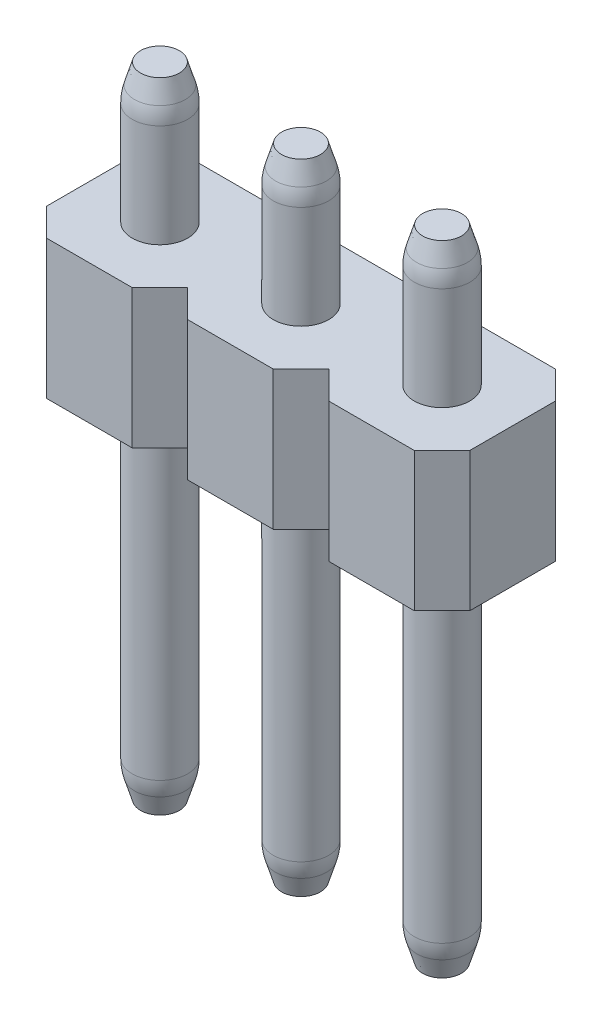
SolidWorks part; units mm, degrees
material "Brass"
ref_plane "Front Plane" through (0, 0, 0) normal (0, 0, 1) x (1, 0, 0)
ref_plane "Top Plane" through (0, 0, 0) normal (0, 1, 0) x (1, 0, 0)
ref_plane "Right Plane" through (0, 0, 0) normal (1, 0, 0) x (0, 0, -1)
sketch "Sketch1" plane through (0, 0, 0) normal (0, 1, 0) x (1, 0, 0)
  line L0 (0, 0) -> (2.54, 0) construction
  circle A0 centre (0, 0) radius 0.5
  circle A1 centre (2.54, 0) radius 0.5
  circle A2 centre (5.08, 0) radius 0.5
  circle A3 centre (7.62, 0) radius 0.5
  circle A4 centre (10.16, 0) radius 0.5
  circle A5 centre (12.7, 0) radius 0.5
  circle A6 centre (15.24, 0) radius 0.5
  circle A7 centre (17.78, 0) radius 0.5
  circle A8 centre (20.32, 0) radius 0.5
  circle A9 centre (22.86, 0) radius 0.5
  circle A10 centre (25.4, 0) radius 0.5
  circle A11 centre (27.94, 0) radius 0.5
  circle A12 centre (30.48, 0) radius 0.5
  circle A13 centre (33.02, 0) radius 0.5
  circle A14 centre (35.56, 0) radius 0.5
  circle A15 centre (38.1, 0) radius 0.5
  dimension "D1" = 1
  dimension "D3" = 2.54
  dimension "D2" = 16
extrude "Boss-Extrude1" add sketch "Sketch1" along normal blind 11.5
ref_plane "Plane1" through (0, 6.5, 0) normal (0, 1, 0) x (1, 0, 0)
sketch "Sketch2" plane through (0, 6.5, 0) normal (0, 1, 0) x (1, 0, 0)
  line L0 (-1.27, 0.77) -> (-0.77, 1.27)
  line L1 (-0.77, -1.27) -> (0.77, -1.27)
  line L2 (-1.27, -0.77) -> (-1.27, 0.77)
  line L3 (-0.77, 1.27) -> (0.77, 1.27)
  line L5 (-1.27, -1.27) -> (1.27, 1.27) construction
  line L6 (-1.27, 1.27) -> (1.27, -1.27) construction
  line L7 (0.77, 1.27) -> (1.27, 0.77)
  line L8 (0.77, -1.27) -> (1.27, -0.77)
  line L9 (-1.27, -0.77) -> (-0.77, -1.27)
  line L10 (1.27, 0.77) -> (1.77, 1.27)
  line L11 (1.77, 1.27) -> (3.31, 1.27)
  line L12 (3.31, 1.27) -> (3.81, 0.77)
  line L14 (3.31, -1.27) -> (3.81, -0.77)
  line L15 (1.77, -1.27) -> (3.31, -1.27)
  line L16 (1.27, -0.77) -> (1.77, -1.27)
  line L17 (3.81, 0.77) -> (4.31, 1.27)
  line L18 (4.31, 1.27) -> (5.85, 1.27)
  line L19 (5.85, 1.27) -> (6.35, 0.77)
  line L20 (6.35, -0.77) -> (6.35, 0.77) construction
  line L21 (5.85, -1.27) -> (6.35, -0.77)
  line L22 (4.31, -1.27) -> (5.85, -1.27)
  line L23 (3.81, -0.77) -> (4.31, -1.27)
  line L24 (6.35, 0.77) -> (6.85, 1.27)
  line L25 (6.85, 1.27) -> (8.39, 1.27)
  line L26 (8.39, 1.27) -> (8.89, 0.77)
  line L27 (8.89, -0.77) -> (8.89, 0.77) construction
  line L28 (8.39, -1.27) -> (8.89, -0.77)
  line L29 (6.85, -1.27) -> (8.39, -1.27)
  line L30 (6.35, -0.77) -> (6.85, -1.27)
  line L31 (8.89, 0.77) -> (9.39, 1.27)
  line L32 (9.39, 1.27) -> (10.93, 1.27)
  line L33 (10.93, 1.27) -> (11.43, 0.77)
  line L34 (11.43, -0.77) -> (11.43, 0.77) construction
  line L35 (10.93, -1.27) -> (11.43, -0.77)
  line L36 (9.39, -1.27) -> (10.93, -1.27)
  line L37 (8.89, -0.77) -> (9.39, -1.27)
  line L38 (11.43, 0.77) -> (11.93, 1.27)
  line L39 (11.93, 1.27) -> (13.47, 1.27)
  line L40 (13.47, 1.27) -> (13.97, 0.77)
  line L41 (13.97, -0.77) -> (13.97, 0.77) construction
  line L42 (13.47, -1.27) -> (13.97, -0.77)
  line L43 (11.93, -1.27) -> (13.47, -1.27)
  line L44 (11.43, -0.77) -> (11.93, -1.27)
  line L45 (13.97, 0.77) -> (14.47, 1.27)
  line L46 (14.47, 1.27) -> (16.01, 1.27)
  line L47 (16.01, 1.27) -> (16.51, 0.77)
  line L48 (16.51, -0.77) -> (16.51, 0.77) construction
  line L49 (16.01, -1.27) -> (16.51, -0.77)
  line L50 (14.47, -1.27) -> (16.01, -1.27)
  line L51 (13.97, -0.77) -> (14.47, -1.27)
  line L52 (16.51, 0.77) -> (17.01, 1.27)
  line L53 (17.01, 1.27) -> (18.55, 1.27)
  line L54 (18.55, 1.27) -> (19.05, 0.77)
  line L55 (19.05, -0.77) -> (19.05, 0.77) construction
  line L56 (18.55, -1.27) -> (19.05, -0.77)
  line L57 (17.01, -1.27) -> (18.55, -1.27)
  line L58 (16.51, -0.77) -> (17.01, -1.27)
  line L59 (19.05, 0.77) -> (19.55, 1.27)
  line L60 (19.55, 1.27) -> (21.09, 1.27)
  line L61 (21.09, 1.27) -> (21.59, 0.77)
  line L62 (21.59, -0.77) -> (21.59, 0.77) construction
  line L63 (21.09, -1.27) -> (21.59, -0.77)
  line L64 (19.55, -1.27) -> (21.09, -1.27)
  line L65 (19.05, -0.77) -> (19.55, -1.27)
  line L66 (21.59, 0.77) -> (22.09, 1.27)
  line L67 (22.09, 1.27) -> (23.63, 1.27)
  line L68 (23.63, 1.27) -> (24.13, 0.77)
  line L69 (24.13, -0.77) -> (24.13, 0.77) construction
  line L70 (23.63, -1.27) -> (24.13, -0.77)
  line L71 (22.09, -1.27) -> (23.63, -1.27)
  line L72 (21.59, -0.77) -> (22.09, -1.27)
  line L73 (24.13, 0.77) -> (24.63, 1.27)
  line L74 (24.63, 1.27) -> (26.17, 1.27)
  line L75 (26.17, 1.27) -> (26.67, 0.77)
  line L76 (26.67, -0.77) -> (26.67, 0.77) construction
  line L77 (26.17, -1.27) -> (26.67, -0.77)
  line L78 (24.63, -1.27) -> (26.17, -1.27)
  line L79 (24.13, -0.77) -> (24.63, -1.27)
  line L80 (26.67, 0.77) -> (27.17, 1.27)
  line L81 (27.17, 1.27) -> (28.71, 1.27)
  line L82 (28.71, 1.27) -> (29.21, 0.77)
  line L83 (29.21, -0.77) -> (29.21, 0.77) construction
  line L84 (28.71, -1.27) -> (29.21, -0.77)
  line L85 (27.17, -1.27) -> (28.71, -1.27)
  line L86 (26.67, -0.77) -> (27.17, -1.27)
  line L87 (29.21, 0.77) -> (29.71, 1.27)
  line L88 (29.71, 1.27) -> (31.25, 1.27)
  line L89 (31.25, 1.27) -> (31.75, 0.77)
  line L90 (31.75, -0.77) -> (31.75, 0.77) construction
  line L91 (31.25, -1.27) -> (31.75, -0.77)
  line L92 (29.71, -1.27) -> (31.25, -1.27)
  line L93 (29.21, -0.77) -> (29.71, -1.27)
  line L94 (31.75, 0.77) -> (32.25, 1.27)
  line L95 (32.25, 1.27) -> (33.79, 1.27)
  line L96 (33.79, 1.27) -> (34.29, 0.77)
  line L97 (34.29, -0.77) -> (34.29, 0.77) construction
  line L98 (33.79, -1.27) -> (34.29, -0.77)
  line L99 (32.25, -1.27) -> (33.79, -1.27)
  line L100 (31.75, -0.77) -> (32.25, -1.27)
  line L101 (34.29, 0.77) -> (34.79, 1.27)
  line L102 (34.79, 1.27) -> (36.33, 1.27)
  line L103 (36.33, 1.27) -> (36.83, 0.77)
  line L104 (36.83, -0.77) -> (36.83, 0.77) construction
  line L105 (36.33, -1.27) -> (36.83, -0.77)
  line L106 (34.79, -1.27) -> (36.33, -1.27)
  line L107 (34.29, -0.77) -> (34.79, -1.27)
  line L108 (36.83, 0.77) -> (37.33, 1.27)
  line L109 (37.33, 1.27) -> (38.87, 1.27)
  line L110 (38.87, 1.27) -> (39.37, 0.77)
  line L111 (39.37, -0.77) -> (39.37, 0.77)
  line L112 (38.87, -1.27) -> (39.37, -0.77)
  line L113 (37.33, -1.27) -> (38.87, -1.27)
  line L114 (36.83, -0.77) -> (37.33, -1.27)
  line L115 (-1.27, 0.77) -> (1.27, 0.77) construction
  point P0 (0, 0)
  dimension "D1" = 2.54
  dimension "D2" = 2.54
  dimension "D4" = 2.54
  dimension "D3" = 16
extrude "Boss-Extrude2" add sketch "Sketch2" along normal blind 2.5
chamfer "Chamfer1" distance 0.5 distance2 0.15 16 edges at (15.24, 11.5, 0.5) (12.7, 11.5, 0.5) (10.16, 11.5, 0.5) (7.62, 11.5, 0.5) (5.08, 11.5, 0.5) (2.54, 11.5, 0.5) (0, 11.5, 0.5) (38.1, 11.5, 0.5) (35.56, 11.5, 0.5) (33.02, 11.5, 0.5) (30.48, 11.5, 0.5) (27.94, 11.5, 0.5) (25.4, 11.5, 0.5) (22.86, 11.5, 0.5) (20.32, 11.5, 0.5) (17.78, 11.5, 0.5) first distance on face at (15.24, 11.5, 0.5) first distance on face at (12.7, 11.5, 0.5) first distance on face at (10.16, 11.5, 0.5) first distance on face at (7.62, 11.5, 0.5) first distance on face at (5.08, 11.5, 0.5) first distance on face at (2.54, 11.5, 0.5) first distance on face at (0, 11.5, 0.5) first distance on face at (38.1, 11.5, 0.5) first distance on face at (35.56, 11.5, 0.5) first distance on face at (33.02, 11.5, 0.5) first distance on face at (30.48, 11.5, 0.5) first distance on face at (27.94, 11.5, 0.5) first distance on face at (25.4, 11.5, 0.5) first distance on face at (22.86, 11.5, 0.5) first distance on face at (20.32, 11.5, 0.5) first distance on face at (17.78, 11.5, 0.5)
fillet "Fillet1" radius 1 16 edges at (38.1, 11, 0.5) (35.56, 11, 0.5) (33.02, 11, 0.5) (30.48, 11, 0.5) (27.94, 11, 0.5) (25.4, 11, 0.5) (22.86, 11, 0.5) (20.32, 11, 0.5) (17.78, 11, 0.5) (15.24, 11, 0.5) (12.7, 11, 0.5) (10.16, 11, 0.5) (7.62, 11, 0.5) (5.08, 11, 0.5) (2.54, 11, 0.5) (0, 11, 0.5)
chamfer "Chamfer2" distance 0.15 distance2 0.5 16 edges at (10.16, 0, 0.5) (17.78, 0, 0.5) (22.86, 0, 0.5) (27.94, 0, 0.5) (30.48, 0, 0.5) (0, 0, 0.5) (2.54, 0, 0.5) (5.08, 0, 0.5) (7.62, 0, 0.5) (12.7, 0, 0.5) (15.24, 0, 0.5) (20.32, 0, 0.5) (25.4, 0, 0.5) (33.02, 0, 0.5) (35.56, 0, 0.5) (38.1, 0, 0.5) first distance on face at (10.16, 0, 0.5) first distance on face at (17.78, 0, 0.5) first distance on face at (22.86, 0, 0.5) first distance on face at (27.94, 0, 0.5) first distance on face at (30.48, 0, 0.5) first distance on face at (0, 0, 0.5) first distance on face at (2.54, 0, 0.5) first distance on face at (5.08, 0, 0.5) first distance on face at (7.62, 0, 0.5) first distance on face at (12.7, 0, 0.5) first distance on face at (15.24, 0, 0.5) first distance on face at (20.32, 0, 0.5) first distance on face at (25.4, 0, 0.5) first distance on face at (33.02, 0, 0.5) first distance on face at (35.56, 0, 0.5) first distance on face at (38.1, 0, 0.5)
fillet "Fillet2" radius 1 16 edges at (30.48, 0.5, 0.5) (33.02, 0.5, 0.5) (35.56, 0.5, 0.5) (38.1, 0.5, 0.5) (27.94, 0.5, 0.5) (25.4, 0.5, 0.5) (22.86, 0.5, 0.5) (20.32, 0.5, 0.5) (17.78, 0.5, 0.5) (15.24, 0.5, 0.5) (12.7, 0.5, 0.5) (10.16, 0.5, 0.5) (7.62, 0.5, 0.5) (5.08, 0.5, 0.5) (2.54, 0.5, 0.5) (0, 0.5, 0.5)
sketch "Sketch3" plane through (0, 0, -1.27) normal (0, 0, -1) x (-1, 0, 0)
  line L0 (-31.75, 9) -> (-31.75, 6.5) construction
  line L1 (-31.75, 11.5) -> (-31.75, 0)
  line L2 (-24.13, 9) -> (-24.13, 6.5) construction
  line L3 (-24.13, 11.5) -> (-24.13, 0)
  line L4 (-31.75, 0) -> (-40.2825, 0)
  line L5 (-40.2825, 0) -> (-40.2825, 14.7026)
  line L6 (-40.2825, 14.7026) -> (-31.75, 11.5)
  line L7 (-24.13, 11.5) -> (2.3615, 11.5)
  line L8 (2.3615, 11.5) -> (2.4072, -1.428)
  line L9 (2.4072, -1.428) -> (-24.13, 0)
extrude "Cut-Extrude1" cut sketch "Sketch3" against normal through all both and the other way through all
